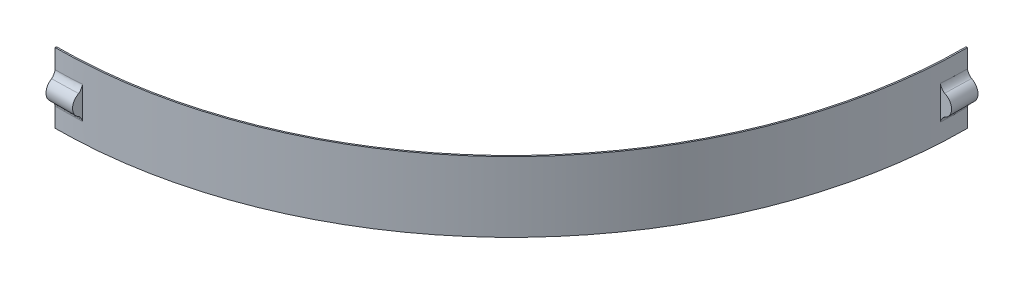
SolidWorks part; units mm, degrees
ref_plane "Front Plane" through (0, 0, 0) normal (0, 0, 1) x (1, 0, 0)
ref_plane "Top Plane" through (0, 0, 0) normal (0, 1, 0) x (1, 0, 0)
ref_plane "Right Plane" through (0, 0, 0) normal (1, 0, 0) x (0, 0, -1)
sketch "Sketch1" plane through (0, 0, 0) normal (0, 0, 1) x (1, 0, 0)
  line L0 (0, 3.3639) -> (0, -36.2756) construction
  line L1 (165.6842, 12.7) -> (165.1762, 12.7)
  line L2 (165.6842, 12.7) -> (165.6842, -12.7)
  line L3 (165.6842, -12.7) -> (165.1762, -12.7)
  line L4 (165.1762, 12.7) -> (165.1762, -12.7)
  line L5 (165.6842, 12.7) -> (165.1762, -12.7) construction
  line L6 (165.6842, -12.7) -> (165.1762, 12.7) construction
  point P0 (165.4302, 0)
  dimension "D1" = 25.4
  dimension "D2" = 0.508
  dimension "D3" = 165.4302
revolve "Revolve1" add sketch "Sketch1" angle 90 about L0
sketch "Sketch4" plane through (0, 0, 0) normal (-1, 0, 0) x (0, 0, 1)
  line L0 (165.1762, 12.7) -> (165.1762, -12.7) construction
  circle A0 centre (164.9222, 0) radius 4.064
  point P2 (165.1762, 0)
  dimension "D2" = 8.128
  dimension "D1" = 0.254
extrude "Boss-Extrude1" add sketch "Sketch4" against normal blind 9.652
sketch "Sketch6" plane through (9.652, 0, 0) normal (1, 0, 0) x (0, 0, -1)
  circle A0 centre (-164.9222, 0) radius 3.175
  circle A2 centre (-164.9222, 0) radius 4.064 construction
  dimension "D1" = 6.35
fillet "Fillet6" radius 2.54 2 edges at (8.128, 4.0249, 165.4847) (1.5263, -3.9933, 165.6772) conic radius 5.08
fillet "Fillet8" radius 2.54 2 edges at (8.128, -4.0636, 164.9761) (1.5262, 4.0565, 165.1691) conic radius 5.08
sketch "Sketch7" plane through (0, 0, 0) normal (0, 0, -1) x (-1, 0, 0)
  line L0 (-165.6842, -12.7) -> (-165.6842, 12.7) construction
  circle A0 centre (-165.4302, 0) radius 4.064
  point P2 (-165.6842, 0)
  dimension "D1" = 8.128
  dimension "D2" = 0.254
extrude "Boss-Extrude2" add sketch "Sketch7" against normal blind 9.6012
sketch "Sketch8" plane through (0, 0, 9.6012) normal (0, 0, 1) x (1, 0, 0)
  circle A0 centre (165.4302, 0) radius 3.175
  circle A1 centre (165.4302, 0) radius 4.064 construction
  dimension "D1" = 6.35
fillet "Fillet11" radius 2.54 4 edges at (165.1696, -4.0556, 1.4753) (164.9761, 4.0386, 8.128) (165.4847, -4.0636, 8.128) (165.6776, 4.0565, 1.4753) conic radius 5.08
sketch "Sketch9" plane through (0, 0, 0) normal (-1, 0, 0) x (0, 0, 1)
  circle A0 centre (164.9222, 0) radius 3.175
  dimension "D1" = 6.35
extrude "Cut-Extrude1" cut sketch "Sketch9" against normal blind 9.525
sketch "Sketch10" plane through (0, 0, 0) normal (0, 0, -1) x (-1, 0, 0)
  circle A0 centre (-165.4302, 0) radius 3.175
extrude "Cut-Extrude2" cut sketch "Sketch10" against normal blind 9.525
